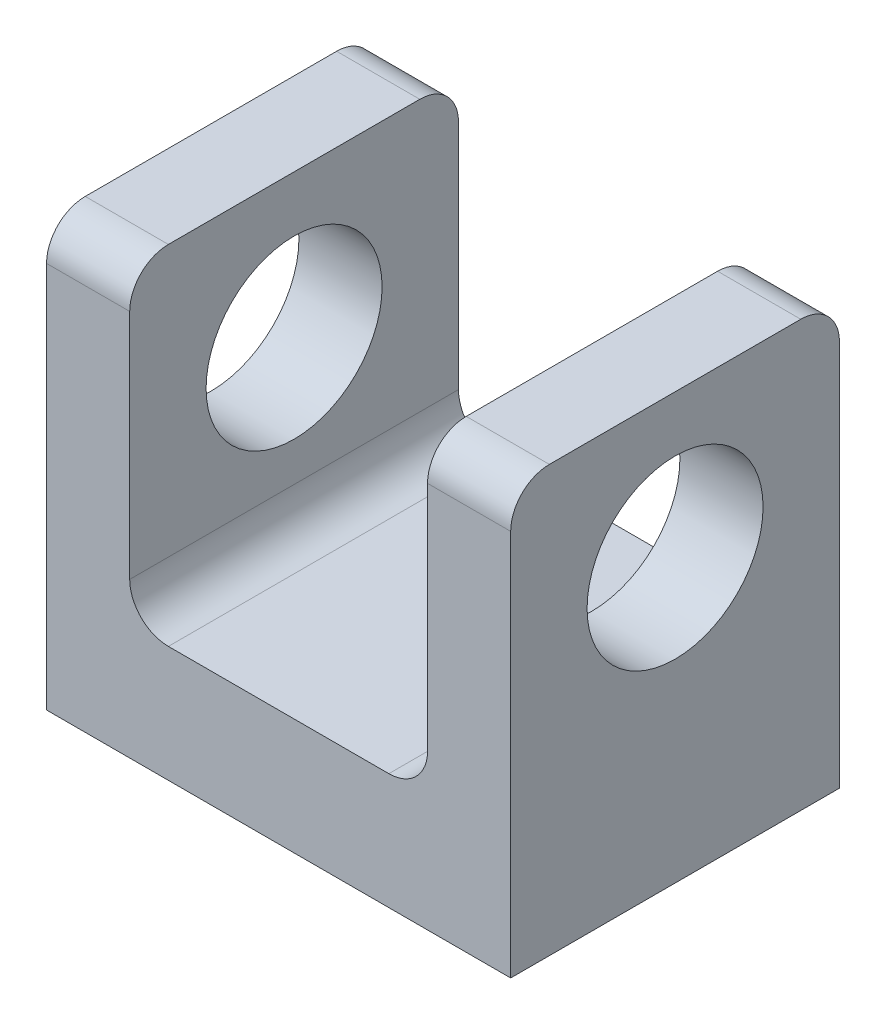
SolidWorks part; units mm, degrees
material "7075-O (SS)"
ref_plane "Front Plane" through (0, 0, 0) normal (0, 0, 1) x (1, 0, 0)
ref_plane "Top Plane" through (0, 0, 0) normal (0, 1, 0) x (1, 0, 0)
ref_plane "Right Plane" through (0, 0, 0) normal (1, 0, 0) x (0, 0, -1)
sketch "Sketch1" plane through (0, 0, 0) normal (0, 0, 1) x (1, 0, 0)
  line L1 (-60, -55) -> (60, -55)
  line L2 (-60, -55) -> (-60, 55)
  line L3 (-60, 55) -> (60, 55)
  line L4 (60, -55) -> (60, 55)
  line L5 (-60, -55) -> (60, 55) construction
  line L6 (-60, 55) -> (60, -55) construction
  point P0 (0, 0)
  dimension "D1" = 120
  dimension "D2" = 110
extrude "Boss-Extrude1" add sketch "Sketch1" along normal blind 85
sketch "Sketch2" plane through (0, 0, 85) normal (0, 0, 1) x (1, 0, 0)
  line L0 (60, 55) -> (-60, 55) construction
  line L1 (-38.5, -25) -> (38.5, -25)
  line L2 (-38.5, -25) -> (-38.5, 135)
  line L3 (-38.5, 135) -> (38.5, 135)
  line L4 (38.5, -25) -> (38.5, 135)
  line L5 (-38.5, -25) -> (38.5, 135) construction
  line L6 (-38.5, 135) -> (38.5, -25) construction
  line L7 (-60, -55) -> (60, -55) construction
  point P0 (0, 55)
  dimension "D1" = 77
  dimension "D2" = 30
extrude "Cut-Extrude1" cut sketch "Sketch2" against normal through all
sketch "Sketch3" plane through (-38.5, 0, 0) normal (1, 0, 0) x (0, 0, -1)
  line L0 (-42.5, 55) -> (-42.5, -25) construction
  line L1 (-85, 55) -> (0, 55) construction
  line L2 (0, -25) -> (-85, -25) construction
  circle A0 centre (-42.5, 17.8789) radius 22.75
  dimension "D1" = 45.5
extrude "Hinge Hole" cut sketch "Sketch3" against normal through all both and the other way through all
fillet "Fillet1" radius 10 6 edges at (38.5, -25, 42.5) (-38.5, -25, 42.5) (49.25, 55, 0) (49.25, 55, 85) (-49.25, 55, 0) (-49.25, 55, 85)
